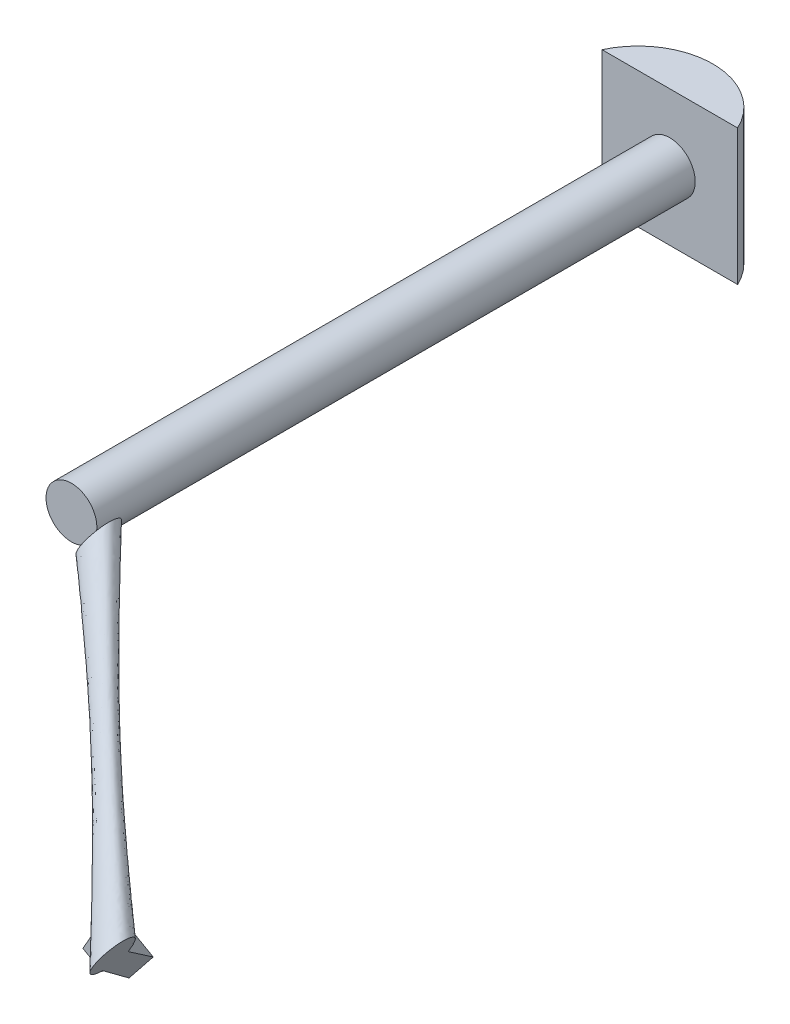
SolidWorks part; units mm, degrees
ref_plane "Front Plane" through (0, 0, 0) normal (0, 0, 1) x (1, 0, 0)
ref_plane "Top Plane" through (0, 0, 0) normal (0, 1, 0) x (1, 0, 0)
ref_plane "Right Plane" through (0, 0, 0) normal (1, 0, 0) x (0, 0, -1)
sketch "Sketch1" plane through (0, 0, 0) normal (0, 0, 1) x (1, 0, 0)
  circle A0 centre (0, 0) radius 2.3813
  dimension "D1" = 4.7625
extrude "Boss-Extrude1" add sketch "Sketch1" along normal blind 58.5966
sketch "Sketch2" plane through (0, 0, 0) normal (0, 1, 0) x (1, 0, 0)
  line L0 (0, -2.5637) -> (6.35, -2.5637)
  line L1 (6.35, -2.5637) -> (-6.35, -2.5637)
  arc A0 (-6.35, -2.5637) -> (6.35, -2.5637) centre (0, -5.5378) cw
  dimension "D1" = 6.35
  dimension "D2" = 12.7
extrude "Boss-Extrude2" add sketch "Sketch2" along normal mid plane 12.7 contours A0 L1 L0 region at (0, 0, 0.9006)
ref_plane "Plane1" through (2.07, -1.177, 0) normal (0.8693, -0.4943, 0) x (0, 0, -1)
ref_plane "Plane2" through (24.1501, -13.7321, 0) normal (0.8693, -0.4943, 0) x (0, 0, -1)
sketch "Sketch4" plane through (2.07, -1.177, 0) normal (0.8693, -0.4943, 0) x (0, 0, -1)
  circle A0 centre (-58.1131, 0) radius 1.9126
sketch "Sketch5" plane through (24.1501, -13.7321, 0) normal (0.8693, -0.4943, 0) x (0, 0, -1)
  circle A0 centre (-78.8962, 0) radius 1.9126
loft "Loft1" add profiles "Sketch5", "Sketch4" connector at (24.6354, -12.8786, 80.5375) connector at (2.7676, 0.0498, 56.8224)
ref_point "Point1"
sketch "Sketch8" plane through (24.1501, -13.7321, 0) normal (0.8693, -0.4943, 0) x (0, 0, -1)
  line L0 (-78.7583, -2.0505) -> (-73.9822, -6.8266)
  line L1 (-78.8962, 0) -> (-76.922, 0)
  line L2 (-78.8962, 0) -> (-78.8962, -2.0505)
  line L3 (-78.8962, -2.0505) -> (-78.7583, -2.0505)
  line L4 (-76.922, 0) -> (-76.922, -1.0253)
  line L5 (-73.9822, -6.8266) -> (-72.4644, -5.3088)
  line L6 (-72.4644, -5.3088) -> (-76.922, -1.0253)
extrude "Boss-Extrude4" add sketch "Sketch8" against normal blind 2.032
